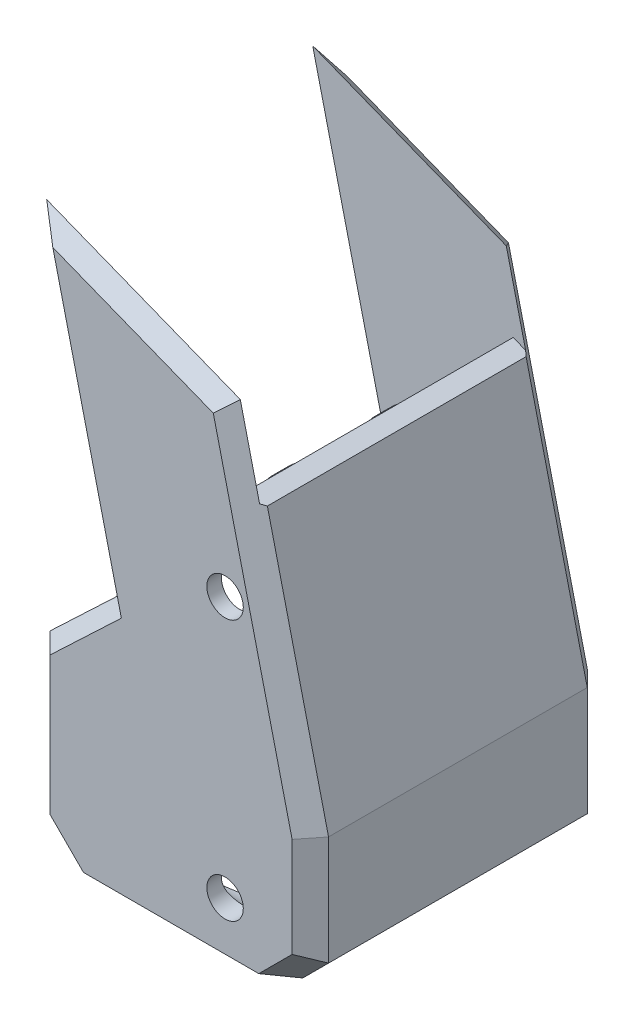
SolidWorks part; units mm, degrees
ref_plane "Front Plane" through (0, 0, 0) normal (0, 0, 1) x (1, 0, 0)
ref_plane "Top Plane" through (0, 0, 0) normal (0, 1, 0) x (1, 0, 0)
ref_plane "Right Plane" through (0, 0, 0) normal (1, 0, 0) x (0, 0, -1)
sketch "Sketch1" plane through (0, 0, 0) normal (0, 0, 1) x (1, 0, 0)
  line L0 (-31.124, 0) -> (31.124, 0)
  line L1 (-31.124, 0) -> (-38.195, 7.0711)
  line L2 (-38.195, 7.0711) -> (-38.195, 49.276)
  line L3 (-38.195, 49.276) -> (-19.191, 67.2738)
  line L4 (-19.191, 67.2738) -> (-39.5606, 152.4971)
  line L5 (-39.5606, 152.4971) -> (15.8274, 130.654)
  line L6 (15.8274, 130.654) -> (38.195, 37.0711)
  line L7 (38.195, 37.0711) -> (38.195, 7.0711)
  line L8 (38.195, 7.0711) -> (31.124, 0)
  point P3 (0, 0)
  dimension "D1" = 62.2479
  dimension "D2" = 135
  dimension "D3" = 135
  dimension "D4" = 10
  dimension "D5" = 30
  dimension "D6" = 96.2189
  dimension "D7" = 59.5395
  dimension "D8" = 87.6238
  dimension "D9" = 26.1739
  dimension "D10" = 42.205
  dimension "D11" = 120
extrude "Boss-Extrude1" add sketch "Sketch1" against normal mid plane 81
sketch "Sketch2" plane through (0, 0, 0) normal (0, 0, 1) x (1, 0, 0)
  line L0 (-38.195, 7.0711) -> (-31.124, 0) construction
  line L17 (-39.5606, 152.4971) -> (-19.191, 67.2738) construction
  line L18 (-38.195, 49.276) -> (-38.195, 7.0711) construction
  line L19 (-19.191, 67.2738) -> (-38.195, 49.276) construction
  line L20 (-38.195, 49.276) -> (-38.195, 7.0711)
  line L21 (-19.191, 67.2738) -> (-38.195, 49.276)
  line L22 (-31.124, 4) -> (29.4671, 4)
  line L23 (29.4671, 4) -> (34.195, 8.7279)
  line L24 (34.195, 8.7279) -> (34.195, 36.5997)
  line L25 (34.195, 36.5997) -> (12.4214, 127.6974)
  line L26 (12.4214, 127.6974) -> (-41.028, 148.776)
  line L27 (-35.124, 4) -> (29.4671, 4)
  line L28 (29.4671, 4) -> (34.195, 8.7279)
  line L29 (34.195, 8.7279) -> (34.195, 36.5997)
  line L30 (34.195, 36.5997) -> (12.4214, 127.6974)
  line L31 (12.4214, 127.6974) -> (-38.4259, 147.7498)
  line L32 (-38.4259, 147.7498) -> (-19.191, 67.2738)
  line L34 (-38.195, 7.0711) -> (-35.124, 4)
  dimension "D1" = 4
extrude "Cut-Extrude1" cut sketch "Sketch2" against normal mid plane 73
sketch "Sketch3" plane through (0, 0, 0) normal (0, 0, 1) x (1, 0, 0)
  line L0 (-39.5606, 152.4971) -> (15.8274, 130.654)
  line L1 (15.8274, 130.654) -> (21.4066, 107.3115)
  line L2 (38.195, 37.0711) -> (15.8274, 130.654) construction
  line L3 (21.4066, 107.3115) -> (-33.9814, 129.1546)
  line L4 (-39.5606, 152.4971) -> (-19.191, 67.2738) construction
  line L5 (-33.9814, 129.1546) -> (-39.5606, 152.4971)
  dimension "D1" = 24
extrude "Cut-Extrude2" cut sketch "Sketch3" against normal mid plane 73
sketch "Sketch8" plane through (0, 0, 0) normal (0, 0, 1) x (1, 0, 0)
  line L0 (14.799, 84.9656) -> (14.799, 81.9656) construction
  line L1 (14.799, 84.9656) -> (14.8797, 81.9667) construction
  line L2 (9.5059, 84.9656) -> (9.5059, 13.3506) construction
  line L3 (9.5059, 13.3506) -> (14.799, 13.3506) construction
  line L4 (16.6468, 16.3495) -> (16.7275, 13.3506) construction
  line L5 (14.799, 15.6485) -> (14.799, 4.3863) construction
  line L6 (38.195, 37.0711) -> (15.8274, 130.654) construction
  line L7 (-31.124, 0) -> (31.124, 0) construction
  circle A0 centre (16.7275, 13.3506) radius 3
  circle A1 centre (14.799, 84.9656) radius 3
  dimension "D1" = 1.543
  dimension "D3" = 6
  dimension "D4" = 5.293
  dimension "D2" = 71.615
  dimension "D5" = 11.6213
  dimension "D6" = 84.9656
sketch "Sketch4" plane through (0, 0, 0) normal (0, 0, 1) x (1, 0, 0)
  line L0 (14.799, 29.1506) -> (34.195, 29.1506)
  line L1 (34.195, 8.7279) -> (34.195, 36.5997) construction
  line L2 (34.195, 29.1506) -> (34.195, 8.7279)
  line L3 (34.195, 8.7279) -> (29.4671, 4)
  line L4 (29.4671, 4) -> (-1.001, 4)
  line L6 (-1.001, 4) -> (-1.001, 13.3506)
  arc A0 (14.799, 29.1506) -> (-1.001, 13.3506) centre (14.799, 13.3506) ccw
  circle A1 centre (14.799, 13.3506) radius 3
  dimension "D1" = 6
  dimension "D2" = 12.8
  dimension "D3" = 9.3506
extrude "Boss-Extrude2" add sketch "Sketch4" along normal mid plane 14
ref_plane "Plane2" through (0, 0, -14) normal (0, 0, 1) x (1, 0, 0)
sketch "Sketch6" plane through (0, 0, -14) normal (0, 0, 1) x (1, 0, 0)
  line L0 (1.8564, 75.8771) -> (36.7015, 26.1132)
  line L1 (34.195, 36.5997) -> (16.8659, 109.1021) construction
  line L2 (36.7015, 26.1132) -> (19.0007, 100.1707)
  line L3 (34.195, 36.5997) -> (16.8659, 109.1021) construction
  line L4 (34.195, 29.1506) -> (14.799, 29.1506) construction
  line L6 (38.195, 7.0711) -> (38.195, 37.0711) construction
  arc A0 (19.0007, 100.1707) -> (1.8564, 75.8771) centre (14.799, 84.9396) ccw
  circle A2 centre (14.799, 84.9396) radius 3
  dimension "D1" = 6
  dimension "D2" = 12.8
  dimension "D3" = 55
  dimension "D4" = 7.6273
  dimension "D5" = 23.3961
extrude "Boss-Extrude3" add sketch "Sketch6" along normal mid plane 12
mirror "Mirror1" about plane through (0, 0, 0) normal (0, 0, 1) of "Boss-Extrude3"
sketch "Sketch7" plane through (0, 4, 0) normal (0, 1, 0) x (1, 0, 0)
  line L4 (-35.124, 36.5) -> (-35.124, -36.5)
  line L5 (29.4671, 36.5) -> (29.4671, 7) construction
  line L6 (29.4671, 23.25) -> (29.4671, 7)
  line L7 (29.4671, 7) -> (-1.001, 7)
  line L8 (-1.001, 7) -> (-1.001, -7)
  line L9 (-1.001, -7) -> (29.4671, -7)
  line L10 (29.4671, -7) -> (29.4671, -23.25)
  line L11 (29.4671, -7) -> (29.4671, -36.5) construction
  line L12 (-1.001, 0) -> (-35.124, 0) construction
  line L13 (15.8274, 36.5) -> (-39.5606, 36.5) construction
  line L14 (-35.124, 36.5) -> (-35.124, -36.5) construction
  line L15 (-35.124, 36.5) -> (29.4671, 23.25)
  line L16 (29.4671, -23.25) -> (-35.124, -36.5)
  dimension "D1" = 16.25
extrude "Cut-Extrude3" cut sketch "Sketch7" against normal through all
fillet "Fillet1" radius 10 8 edges at (34.195, 22.6638, -36.5) (34.195, 22.6638, 36.5) (-2.8284, 4, -36.5) (-2.8284, 4, 36.5) (29.4671, 4, -29.875) (29.4671, 4, 29.875) (34.195, 29.6927, 14) (34.195, 29.6927, -14)
fillet "Fillet3" radius 4 24 edges at (-1.001, 6.6753, -7) (-1.001, 6.6753, 7) (3.6267, 24.5229, -7) (3.6267, 24.5229, 7) (24.497, 29.1506, -7) (24.497, 29.1506, 7) (17.1215, 54.0763, -20) (17.1215, 54.0763, 20) (17.1215, 54.0763, 8) (17.1215, 54.0763, -8) (1.8898, 94.0498, -20) (1.8898, 94.0498, 20) (1.8898, 94.0498, 8) (1.8898, 94.0498, -8) (33.7322, 29.5468, -20) (33.7322, 29.5468, 20) (33.7322, 29.5468, 8) (33.7322, 29.5468, -8) (33.7347, 8.2676, 29.4992) (33.7347, 8.2676, -29.4992) (34.195, 8.7279, 16.75) (34.195, 8.7279, -16.75)
fillet "Fillet4" radius 4 9 edges at (34.195, 17.7677, 7) (34.195, 27.979, 5.8284) (34.195, 17.7677, -7) (34.195, 27.979, -5.8284) (34.195, 29.1506, 0) (31.2453, 5.7782, 7) (33.8905, 8.854, 7) (31.2453, 5.7782, -7) (33.8905, 8.854, -7)
chamfer "Chamfer1" distance 5 angle 45 18 edges at (34.6595, 3.5355, 40.5) (0, 0, 40.5) (-34.6595, 3.5355, 40.5) (-38.195, 28.1736, 40.5) (-28.693, 58.2749, 40.5) (-29.3758, 109.8855, 40.5) (-11.8666, 141.5755, 40.5) (27.0112, 83.8625, 40.5) (38.195, 22.0711, -40.5) (34.6595, 3.5355, -40.5) (0, 0, -40.5) (-34.6595, 3.5355, -40.5) (-38.195, 28.1736, -40.5) (-28.693, 58.2749, -40.5) (-29.3758, 109.8855, -40.5) (-11.8666, 141.5755, -40.5) (27.0112, 83.8625, -40.5) (38.195, 22.0711, 40.5)
sketch "Sketch9" plane through (0, 0, 0) normal (0, 0, 1) x (1, 0, 0)
  line L1 (25.5942, 72.5844) -> (18.4587, 102.4384)
  line L4 (24.195, 78.4382) -> (34.195, 36.5997) construction
  line L5 (22.0264, 87.5114) -> (25.0415, 88.232) construction
  arc A2 (19.0007, 100.1707) -> (1.8564, 75.8771) centre (14.799, 84.9396) ccw construction
  arc A3 (18.4587, 102.4384) -> (25.5942, 72.5844) centre (-13.4162, 79.0401) cw
  dimension "D2" = 0.8211
  dimension "D1" = 29.854
  dimension "D4" = 3.1
extrude "Cut-Extrude4" cut sketch "Sketch9" against normal mid plane 16
fillet "Fillet5" radius 10 2 edges at (18.4587, 102.4384, 0) (25.5942, 72.5844, 0)
chamfer "Chamfer2" [suppressed] distance 2.5 angle 45
sketch "Sketch10" plane through (0, 0, 40.5) normal (0, 0, 1) x (1, 0, 0)
  circle A0 centre (14.799, 84.9396) radius 5
  circle A1 centre (14.799, 84.9396) radius 3 construction
  dimension "D1" = 10
extrude "Cut-Extrude5" cut sketch "Sketch10" against normal blind 10 contours A0
sketch "Sketch11" plane through (0, 0, 40.5) normal (0, 0, 1) x (1, 0, 0)
  circle A0 centre (14.799, 13.3506) radius 5
  circle A1 centre (14.799, 13.3506) radius 3 construction
  dimension "D1" = 10
extrude "Cut-Extrude6" cut sketch "Sketch11" against normal blind 10
mirror "Mirror3" about plane through (0, 0, 0) normal (0, 0, 1) of "Cut-Extrude5", "Cut-Extrude6"
